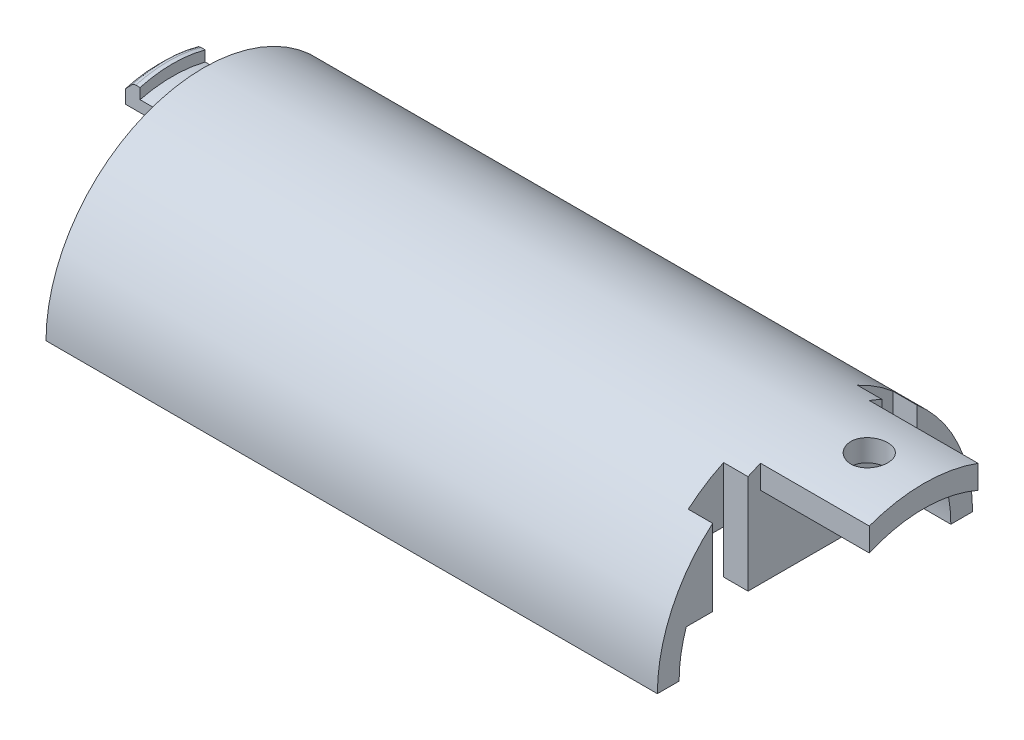
SolidWorks part; units mm, degrees
ref_plane "Alzado" through (0, 0, 0) normal (1, 0, 0) x (0, 1, 0)
ref_plane "Planta" through (0, 0, 0) normal (0, 0, 1) x (0, 1, 0)
ref_plane "Vista lateral" through (0, 0, 0) normal (0, 1, 0) x (-1, 0, 0)
sketch "Croquis2" plane through (0, 0, 0) normal (1, 0, 0) x (0, 1, 0)
  line L0 (0, -14.5) -> (0, 14.5)
  arc A1 (0, -14.5) -> (0, 14.5) centre (0, 0) ccw
  arc A2 (0, -12.5) -> (0, 12.5) centre (0, 0) ccw
  dimension "D1" = 25
  dimension "D2" = 2
extrude "Saliente-Extruir1" add sketch "Croquis2" along normal mid plane 61.75 contours A2 L0 A1 region at (0, 0.3242, -13.5)
ref_plane "Plano1" through (-21.625, 0, 0) normal (1, 0, 0) x (0, 0, -1)
ref_plane "Plano2" through (23.125, 0, 0) normal (1, 0, 0) x (0, 0, -1)
sketch "Croquis3" plane through (-21.625, 0, 0) normal (1, 0, 0) x (0, 0, -1)
  line L0 (-12.5, 0) -> (-3.75, 0)
  line L1 (3.75, 0) -> (12.5, 0)
  arc A0 (12.5, 0) -> (-12.5, 0) centre (0, 0) ccw construction
  arc A1 (12.5, 0) -> (-12.5, 0) centre (0, 0) ccw
  arc A2 (3.75, 0) -> (-3.75, 0) centre (0, 0) ccw
  dimension "D1" = 7.5
extrude "Saliente-Extruir2" add sketch "Croquis3" against normal blind 2
sketch "Croquis4" plane through (23.125, 0, 0) normal (1, 0, 0) x (0, 0, -1)
  line L0 (-11.8427, 4) -> (11.8427, 4)
  line L1 (-9.6047, 8) -> (9.6047, 8)
  line L2 (-4.325, 4) -> (-4.325, -8)
  line L3 (-4.325, -8) -> (4.325, -8)
  line L4 (4.325, -8) -> (4.325, 4)
  line L5 (0, 0) -> (0, 4) construction
  line L6 (4.325, -6) -> (-4.325, -6)
  line L8 (14.5, 0) -> (12.5, 0) construction
  arc A0 (12.5, 0) -> (-12.5, 0) centre (0, 0) ccw construction
  arc A1 (11.8427, 4) -> (-11.8427, 4) centre (0, 0) ccw
  circle A2 centre (0, 0) radius 3
  point P7 (0, 12.5)
  dimension "D4" = 6
  dimension "D1" = 4.5
  dimension "D2" = 8.5
  dimension "D3" = 8.65
  dimension "D5" = 8
  dimension "D6" = 2
extrude "Saliente-Extruir3" add sketch "Croquis4" against normal blind 20 contours L1 A1 region at (23.125, 9.831, 0)
extrude "Saliente-Extruir4" add sketch "Croquis4<4>" along normal blind 3 contours L1 A1 | L0 A1 L1 region at (23.125, 5.9321, 0) region at (23.125, 9.831, 0)
sketch "Croquis4<4>" plane through (23.125, 0, 0) normal (1, 0, 0) x (0, 0, -1) same geometry as "Croquis4"
ref_plane "Plano4" through (0, 13.5, 0) normal (0, 1, 0) x (-1, 0, 0)
sketch "Croquis6" plane through (0, 13.5, 0) normal (0, 1, 0) x (-1, 0, 0)
  line L0 (30.875, -14.5) -> (30.875, 14.5) construction
  line L1 (30.875, -14.5) -> (30.875, 14.5) construction
  line L2 (28.875, -3) -> (30.875, -3)
  line L3 (28.875, -3) -> (28.875, 3)
  line L4 (30.875, -3) -> (30.875, 3)
  line L5 (28.875, 3) -> (30.875, 3)
  line L6 (28.875, -3) -> (30.875, 3) construction
  line L7 (30.875, -3) -> (28.875, 3) construction
  point P3 (29.875, 0)
  point P11 (30.875, 0)
  dimension "D1" = 6
  dimension "D2" = 2
extrude "Saliente-Extruir6" add sketch "Croquis6" against normal blind 2.5
sketch "Croquis7" plane through (-30.875, 0, 0) normal (-1, 0, 0) x (0, -1, 0)
  line L0 (-11, -3) -> (-11, 3) construction
  line L1 (-11, -3) -> (-11, 3) construction
  line L3 (-11, 3) -> (-12.0334, 3)
  line L4 (-11, 3) -> (-11, -3)
  line L5 (-11, -3) -> (-12.0334, -3)
  arc A0 (-12.0334, 3) -> (-12.0334, -3) centre (0, 0) ccw
  arc A1 (-11, 3) -> (-11, -3) centre (0, 0) ccw
  point P2 (-12.4018, 0)
  point P3 (-11.4018, 0)
  line M9 (-12.1347, -3) -> (-11, -3)
  line M10 (-11, -3) -> (-11, 3)
  line M11 (-11, 3) -> (-12.1347, 3)
  dimension "D1" = 1
extrude "Cortar-Extruir1" cut sketch "Croquis7" against normal up to next contours A1 M10 region at (-30.875, 11.1609, 0)
extrude "Saliente-Extruir7" add sketch "Croquis7<4>" along normal blind 4.2 contours A1 A0 M11 M9 region at (-30.875, 11.7731, 0)
sketch "Croquis7<4>" plane through (-30.875, 0, 0) normal (-1, 0, 0) x (0, -1, 0) same geometry as "Croquis7"
sketch "Croquis8" plane through (-35.075, 0, 0) normal (-1, 0, 0) x (0, -1, 0)
  line L0 (-11, 3) -> (-13, 3)
  line L1 (-13.4018, 0) -> (-11.4018, 0) construction
  line L4 (-13, -3) -> (-11, -3)
  arc A0 (-13, -3) -> (-13, 3) centre (-2, 0) cw
  arc A3 (-11, 3) -> (-11, -3) centre (0, 0) ccw construction
  arc A4 (-11, 3) -> (-11, -3) centre (0, 0) ccw
  point P2 (-13.4018, 0)
  point P9 (-11.4018, 0)
  dimension "D1" = 2
  dimension "D2" = 2
extrude "Saliente-Extruir9" add sketch "Croquis8" against normal blind 1.35
chamfer "Chaflán3" distance 0.75 angle 45 1 edges at (-35.075, 13.4018, 0)
fillet "Redondeo1" radius 0.5 1 edges at (-34.325, 13.4018, 0)
chamfer "Chaflán4" distance 1 angle 45 1 edges at (-28.875, 12.5, 0)
sketch "Croquis9" plane through (30.875, 0, 0) normal (1, 0, 0) x (0, 1, 0)
  line L1 (4, 11.8427) -> (4, -11.8427)
  line L2 (0, -12.5) -> (0, -14.5)
  line L3 (0, 14.5) -> (0, 12.5)
  line L4 (0, -12.5) -> (0, -14.5)
  line L5 (0, 14.5) -> (0, 12.5)
  line L6 (4, 11.8427) -> (4, -11.8427)
  arc A1 (4, -11.8427) -> (4, 11.8427) centre (0, 0) ccw
  arc A2 (0, -12.5) -> (0, 12.5) centre (0, 0) ccw
  arc A3 (0, -14.5) -> (0, 14.5) centre (0, 0) ccw
  arc A4 (0, -12.5) -> (0, 12.5) centre (0, 0) ccw
  arc A5 (0, -14.5) -> (0, 14.5) centre (0, 0) ccw
  arc A6 (4, -11.8427) -> (4, 11.8427) centre (0, 0) ccw
  arc M5 (0, 12.5) -> (0, -12.5) centre (0, 0) cw
  line M6 (0, -12.5) -> (0, -14.5)
  arc M7 (0, -14.5) -> (0, 14.5) centre (0, 0) ccw
  line M8 (0, 14.5) -> (0, 12.5)
  dimension "D1" = 0
  dimension "D2" = 0
extrude "Cortar-Extruir2" cut sketch "Croquis9" against normal blind 5.5 contours L6 M5 | M8 M5 M6 M7 region at (30.875, 7.5239, 0) region at (30.875, 2.0794, 12.6545)
sketch "Croquis10" plane through (25.375, 0, 0) normal (1, 0, 0) x (0, 1, 0)
  line L0 (11.4564, 5) -> (13.6107, 5)
  line L1 (11.4564, -5) -> (13.6107, -5)
  line L2 (14.5, 0) -> (12.5, 0) construction
  arc A0 (0, -12.5) -> (0, 12.5) centre (0, 0) ccw construction
  arc A1 (11.4564, -5) -> (11.4564, 5) centre (0, 0) ccw
  arc A4 (0, -14.5) -> (0, 14.5) centre (0, 0) ccw construction
  arc A5 (13.6107, -5) -> (13.6107, 5) centre (0, 0) ccw
  dimension "D1" = 5
extrude "Saliente-Extruir10" add sketch "Croquis10" along normal blind 10
ref_plane "Plano5" through (0, 14.5, 0) normal (0, 1, 0) x (-1, 0, 0)
sketch "Croquis11" plane through (0, 14.5, 0) normal (0, 1, 0) x (-1, 0, 0)
  line L0 (-35.375, 5) -> (-25.375, -5) construction
  circle A0 centre (-30.375, 0) radius 1.7
  point P4 (-30.375, 0)
  dimension "D1" = 3.4
extrude "Cortar-Extruir3" cut sketch "Croquis11" against normal up to next
sketch "Croquis14" plane through (0, 4, 0) normal (0, -1, 0) x (1, 0, 0)
  line L0 (25.375, 11.8427) -> (25.375, -11.8427) construction
  line L1 (25.375, 9.41) -> (23.125, 9.41)
  line L2 (25.375, 9.41) -> (25.375, 6.16)
  line L3 (25.375, 6.16) -> (23.125, 6.16)
  line L4 (23.125, 9.41) -> (23.125, 6.16)
  line L5 (23.125, 11.8427) -> (23.125, -11.8427) construction
  line L6 (0, 0) -> (10.089, 0) construction
  line L7 (25.375, -9.41) -> (23.125, -9.41)
  line L8 (25.375, -9.41) -> (25.375, -6.16)
  line L9 (25.375, -6.16) -> (23.125, -6.16)
  line L10 (23.125, -9.41) -> (23.125, -6.16)
  point P15 (25.375, 7.785)
  point P16 (25.375, -7.785)
  dimension "D1" = 15.57
  dimension "D2" = 3.25
extrude "Cortar-Extruir6" cut sketch "Croquis14" against normal through all
equation "\"D2@Croquis8\"=\"D1@Croquis8\""
